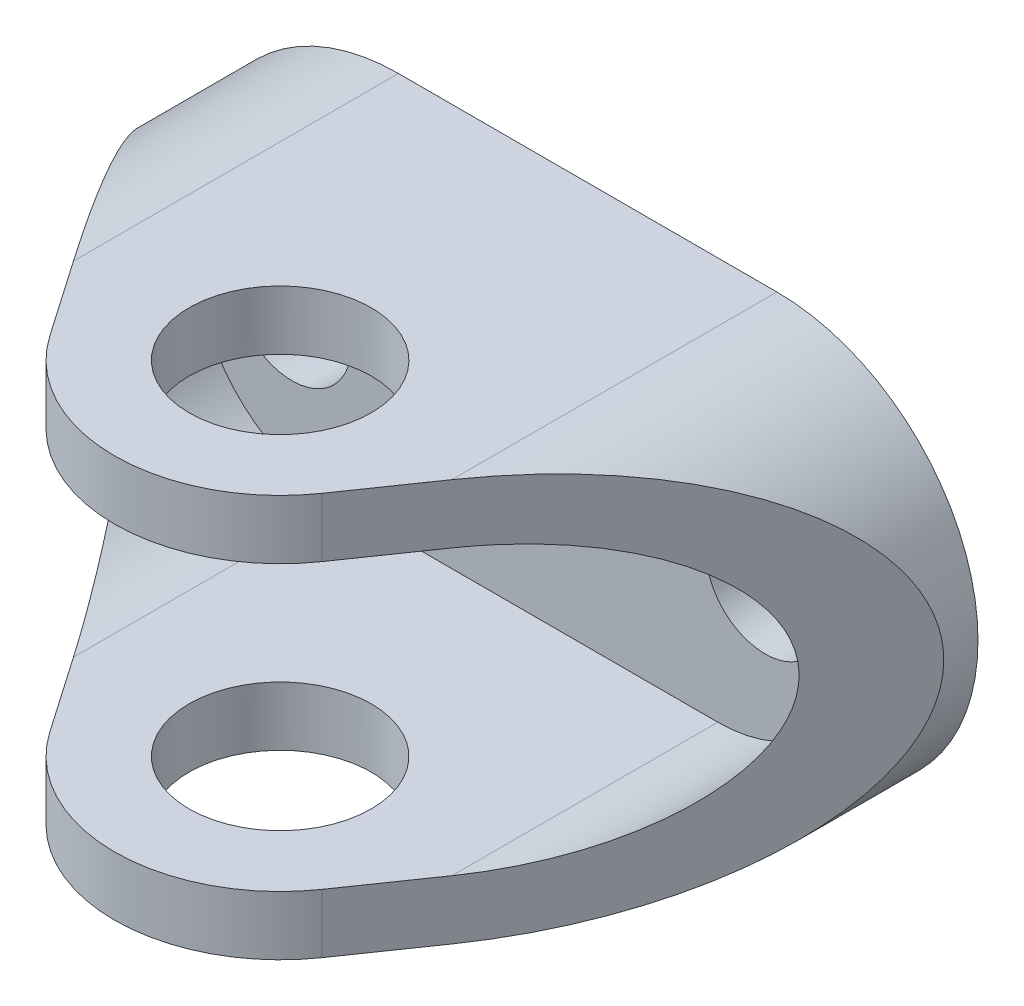
SolidWorks part; units mm, degrees
material "6061 Alloy"
ref_plane "Front Plane" through (0, 0, 0) normal (0, 0, 1) x (1, 0, 0)
ref_plane "Top Plane" through (0, 0, 0) normal (0, 1, 0) x (1, 0, 0)
ref_plane "Right Plane" through (0, 0, 0) normal (1, 0, 0) x (0, 0, -1)
sketch "Sketch1" plane through (0, 0, 0) normal (0, 1, 0) x (1, 0, 0)
  line L0 (-22.225, -15.875) -> (22.225, -15.875)
  line L1 (-22.225, -15.875) -> (-22.225, 15.875)
  line L2 (22.225, -15.875) -> (22.225, 15.875)
  line L3 (-22.225, 15.875) -> (22.225, 15.875)
  line L4 (-22.225, -15.875) -> (22.225, 15.875) construction
  line L5 (22.225, -15.875) -> (-22.225, 15.875) construction
  point P1 (0, 0)
  dimension "D1" = 31.75
  dimension "D2" = 44.45
extrude "Billet" add sketch "Sketch1" along normal blind 21.59
sketch "Sketch2" plane through (0, 21.59, 0) normal (0, 1, 0) x (1, 0, 0)
  line L1 (-7.3121, -5.6913) -> (-22.225, 15.875)
  line L4 (-22.225, 15.875) -> (22.225, 15.875) construction
  line L5 (0, -14.605) -> (0, -11.9174) construction
  line L6 (-22.225, 15.875) -> (-22.225, -15.875)
  line L7 (-22.225, -15.875) -> (22.225, -15.875)
  line L8 (22.225, -15.875) -> (22.225, 15.875)
  line L9 (7.3121, -5.6913) -> (22.225, 15.875)
  line L10 (22.225, 15.875) -> (-22.225, 15.875) construction
  arc A0 (7.3121, -5.6913) -> (-7.3121, -5.6913) centre (0, -0.635) cw
  circle A1 centre (0, -0.635) radius 4.8895
  line M1 (-22.225, 15.875) -> (-22.225, -15.875)
  line M2 (-22.225, -15.875) -> (22.225, -15.875)
  line M3 (22.225, -15.875) -> (22.225, 15.875)
  dimension "D1" = 8.89
  dimension "D3" = 9.779
  dimension "D4" = 16.51
extrude "Mill Cut 1" cut sketch "Sketch2" against normal through all contours L9 A0 L1 M1 M2 M3 | A1 region at (0, 21.59, 10.0712) region at (0, 21.59, 0.635)
ref_plane "Plane2" through (0, 21.59, 9.525) normal (0, 0, 1) x (1, 0, 0)
sketch "Sketch6" plane through (0, 21.59, 9.525) normal (0, 0, 1) x (1, 0, 0)
  line L0 (7.3121, 0) -> (-7.3121, 0) construction
  line L1 (-10.16, -3.175) -> (10.16, -3.175)
  line L3 (-10.16, -18.415) -> (10.16, -18.415)
  line L5 (0, -3.175) -> (0, 0) construction
  line L6 (0, -18.415) -> (0, -21.59) construction
  arc A0 (-10.16, -3.175) -> (-10.16, -18.415) centre (-10.16, -10.795) ccw
  arc A1 (10.16, -3.175) -> (10.16, -18.415) centre (10.16, -10.795) cw
  point P6 (0, 0)
  point P7 (0, -3.175)
  dimension "D1" = 3.175
  dimension "D2" = 10.16
extrude "Cut-Extrude1" cut sketch "Sketch6" against normal offset from surface (22.225 mm away) 3.175 contours L1 L3 region at (0, 10.795, 9.525) up to face at (0, 10.795, -15.875)
sketch "Sketch8" plane through (0, 21.59, 9.525) normal (0, 0, 1) x (1, 0, 0)
  line L7 (-7.3121, 0) -> (-22.225, 0) construction
  line L8 (-10.16, -21.59) -> (-60.96, -21.59)
  line L9 (-60.96, -21.59) -> (-60.96, 0)
  line L10 (-60.96, 0) -> (-10.16, 0)
  line L11 (-7.3121, -21.59) -> (-22.225, -21.59) construction
  arc A4 (-10.16, 0) -> (-10.16, -21.59) centre (-10.16, -10.795) ccw
  arc A8 (-10.16, -3.175) -> (-10.16, -18.415) centre (-10.16, -10.795) ccw construction
  dimension "D1" = 50.8
extrude "Cut-Extrude2" cut sketch "Sketch8" against normal through all
mirror "Mirror1" about plane through (0, 0, 0) normal (1, 0, 0) of "Cut-Extrude2"
sketch "Sketch9" plane through (0, 0, -12.7) normal (0, 0, 1) x (1, 0, 0)
  line L0 (0, 21.59) -> (0, 0) construction
  line L1 (7.3121, 21.59) -> (-7.3121, 21.59) construction
  line L2 (0, 10.795) -> (12.7, 10.795) construction
  circle A0 centre (12.7, 10.795) radius 3.175
  circle A1 centre (-12.7, 10.795) radius 3.175
  dimension "D1" = 6.35
  dimension "D2" = 12.7
extrude "Holes" cut sketch "Sketch9" against normal through all
ref_axis "Axis1" [suppressed] through (0, 18.415, 0.635) along (0, 1, 0)
ref_plane "Plane1" [suppressed] through (0.2984, 0, 0.4261) normal (-0.5736, 0, -0.8192) x (0, 1, 0)
sketch "Sketch5" [suppressed] plane through (0, 21.59, 0) normal (0, 1, 0) x (1, 0, 0)
  circle A0 centre (0, -0.635) radius 4.8895
extrude "Mock Bolt" [suppressed] add sketch "Sketch5" against normal through all
